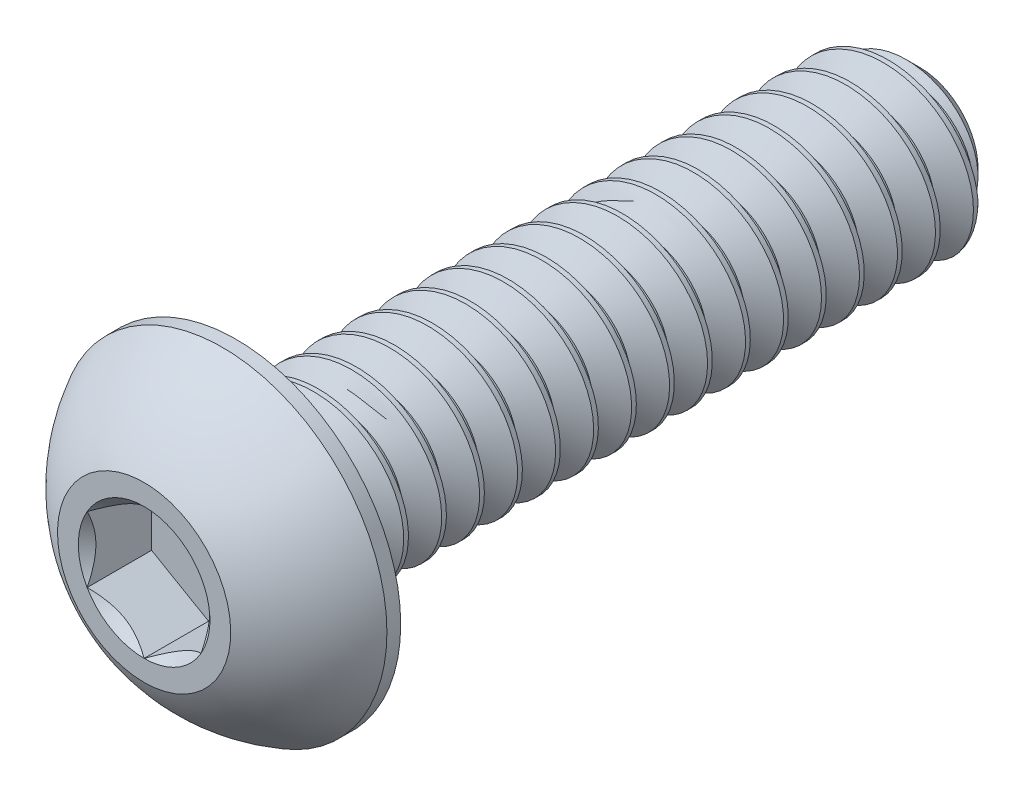
SolidWorks part; units mm, degrees
ref_plane "Front" through (0, 0, 0) normal (0, 0, 1) x (1, 0, 0)
ref_plane "Top" through (0, 0, 0) normal (0, 1, 0) x (1, 0, 0)
ref_plane "Right" through (0, 0, 0) normal (1, 0, 0) x (0, 0, -1)
sketch "Sketch1" plane through (0, 0, 0) normal (1, 0, 0) x (0, 0, -1)
  line L2 (2.5654, 2.413) -> (21.6154, 2.413)
  line L3 (21.6154, 2.413) -> (21.6154, 0)
  line L4 (21.6154, 0) -> (2.5654, 0)
  line L6 (2.1806, 4.5847) -> (2.5654, 4.5847) construction
  line L7 (21.6154, 2.413) -> (21.6154, -2.413) construction
  line L8 (0, 0) -> (2.5654, 0) construction
  line L9 (2.5654, 4.5847) -> (2.5654, -4.5847) construction
  line L11 (2.5654, 2.413) -> (2.5654, 0)
  line L13 (0, 1.5875) -> (0, -1.5875) construction
  line L14 (0, 1.5875) -> (0, 2.413) construction
  arc A3 (0, 2.413) -> (2.1806, 4.5847) centre (4.5749, 0) cw construction
  dimension "D1" = 0.3848
revolve "Revolve1" add sketch "Sketch1" angle 360 mid plane about L4
sketch "Sketch3" plane through (0, 0, -21.6154) normal (0, 0, -1) x (-1, 0, 0)
  circle A0 centre (0, 0) radius 2.413
curve "Helix/Spiral1" pitch 1.0583 height 20.1083 turns 19
sketch "Sketch2" plane through (0, 0, 0) normal (1, 0, 0) x (0, 0, -1)
  line L0 (21.6154, 2.413) -> (22.5414, 2.413)
  line L1 (22.5414, 2.413) -> (22.1446, 1.7256)
  line L2 (22.1446, 1.7256) -> (22.0123, 1.7256)
  line L3 (22.0123, 1.7256) -> (21.6154, 2.413)
  line L4 (21.8138, 2.0693) -> (22.343, 2.0693) construction
  dimension "D1" = 60
  dimension "D2" = 0.1323
  dimension "D3" = 0.5292
chamfer "Chamfer1" distance 0.7937 angle 45 1 edges at (0, 2.413, -21.6154)
sweep "Cut-Sweep1" cut profiles "Sketch2" path "Helix/Spiral1"
sketch "Sketch7" plane through (0, 0, 0) normal (1, 0, 0) x (0, 0, -1)
  line L6 (2.1806, 4.5847) -> (2.5654, 4.5847) construction
  line L8 (0, 0) -> (2.5654, 0) construction
  line L11 (2.5654, 4.5847) -> (2.5654, -4.5847) construction
  line L12 (2.1806, 4.5847) -> (2.5654, 4.5847)
  line L13 (0, 0) -> (2.5654, 0)
  line L14 (0, 1.5875) -> (0, -1.5875) construction
  line L15 (2.5654, 4.5847) -> (2.5654, 0)
  line L16 (0, 2.413) -> (0, 0)
  arc A2 (2.1806, 4.5847) -> (0, 2.413) centre (4.5749, 0) ccw construction
  arc A3 (2.1806, 4.5847) -> (0, 2.413) centre (4.5749, 0) ccw
revolve "Revolve2" add sketch "Sketch7" angle 360 mid plane about L13
sketch "Sketch5" plane through (0, 0, 0) normal (0, 0, 1) x (1, 0, 0)
  line L1 (1.5875, -0.9165) -> (1.5875, 0.9165)
  line L2 (1.5875, 0.9165) -> (0, 1.8331)
  line L3 (0, 1.8331) -> (-1.5875, 0.9165)
  line L4 (-1.5875, 0.9165) -> (-1.5875, -0.9165)
  line L5 (-1.5875, -0.9165) -> (0, -1.8331)
  line L6 (0, -1.8331) -> (1.5875, -0.9165)
  circle A0 centre (0, 0) radius 1.5875 construction
extrude "Cut-Extrude2" cut sketch "Sketch5" against normal blind 1.7958
sketch "Sketch6" plane through (0, 0, 0) normal (0, 0, 1) x (1, 0, 0)
  circle A0 centre (0, 0) radius 1.8331
extrude "Cut-Extrude3" cut sketch "Sketch6" against normal blind 1.7958 draft 45
sketch "Sketch9" [suppressed] plane through (0, 0, -2.5654) normal (0, 0, 1) x (1, 0, 0)
  circle A2 centre (0, 0) radius 2.413
extrude "Boss-Extrude2" [suppressed] add sketch "Sketch9" against normal offset from surface (9.525 mm away) 31.75
sketch "Sketch10" plane through (0, 0, 0) normal (1, 0, 0) x (0, 0, -1)
  line L0 (21.6154, 2.413) -> (21.6154, -2.413) construction
  point P0 (20.0279, -2.413)
  dimension "D1" = 1.5875
equation "\"D3@Helix/Spiral1\" = \"Lg@Sketch1\" + \"D4@Helix/Spiral1\""
equation "\"D2@Sketch2\" = \"D4@Helix/Spiral1\" * .125"
equation "\"D3@Sketch2\" = \"D4@Helix/Spiral1\" * .5"
equation "\"D1@Chamfer1\" = \"D4@Helix/Spiral1\" * .75"
equation "\"D1@Cut-Extrude2\" = \"Head Ht@Sketch1\" * .7"
equation "\"D1@Sketch1\" = \"Head Ht@Sketch1\" * .15"
equation "\"D1@Sketch10\" = \"D4@Helix/Spiral1\" * 1.5"
equation "\"D1@Cut-Extrude3\" = \"D1@Cut-Extrude2\""
